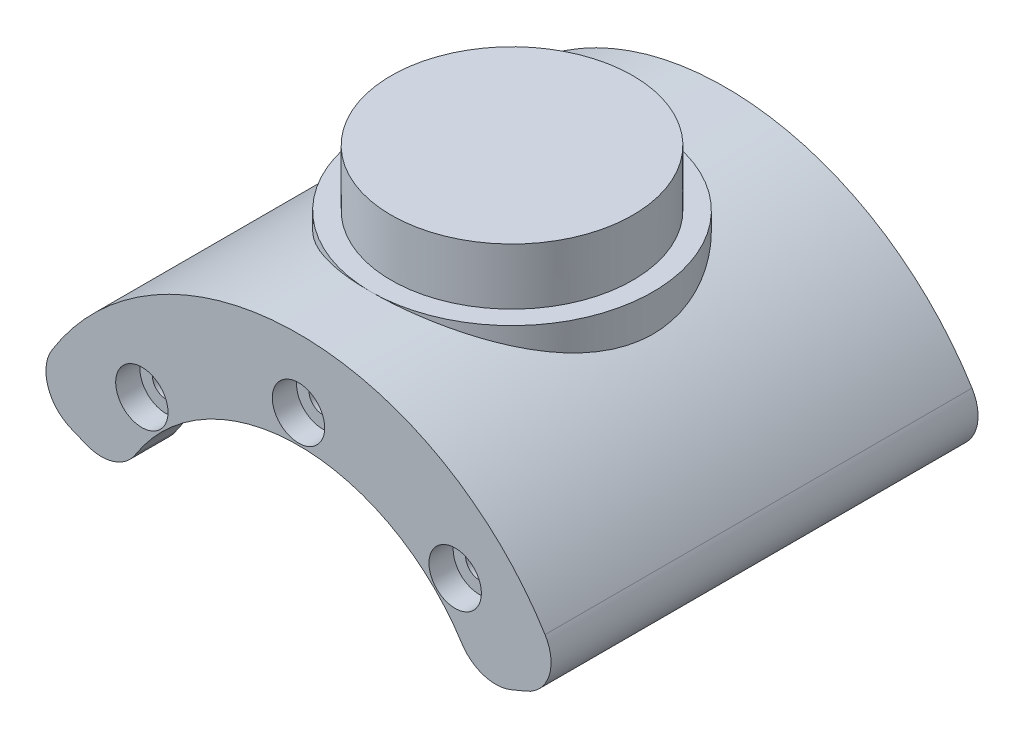
SolidWorks part; units mm, degrees
material "ABS"
ref_plane "Front" through (0, 0, 0) normal (0, 0, 1) x (1, 0, 0)
ref_plane "Top" through (0, 0, 0) normal (0, 1, 0) x (1, 0, 0)
ref_plane "Right" through (0, 0, 0) normal (1, 0, 0) x (0, 0, -1)
sketch "ｽｹｯﾁ1" plane through (0, 0, 0) normal (0, 0, 1) x (1, 0, 0)
  circle A0 centre (0, 0) radius 36
  dimension "D1" = 72
extrude "ﾎﾞｽ - 押し出し1" add sketch "ｽｹｯﾁ1" along normal mid plane 53
sketch "ｽｹｯﾁ5" plane through (0, 0, 0) normal (0, 0, 1) x (1, 0, 0)
  circle A0 centre (0, 0) radius 24
  dimension "D1" = 48
extrude "ｶｯﾄ - 押し出し3" cut sketch "ｽｹｯﾁ5" against normal through all both and the other way through all
sketch "ｽｹｯﾁ6" plane through (0, 0, 26.5) normal (0, 0, 1) x (1, 0, 0)
  line L0 (-33.2597, 13.7766) -> (0, 0)
  line L1 (0, 0) -> (33.2597, 13.7766)
  circle A0 centre (0, 0) radius 36 construction
  arc A1 (-33.2597, 13.7766) -> (33.2597, 13.7766) centre (0, 0) ccw
  dimension "D1" = 135
extrude "ｶｯﾄ - 押し出し4" cut sketch "ｽｹｯﾁ6" against normal through all both and the other way through all
sketch "ｽｹｯﾁ3" plane through (0, 0, 0) normal (0, 0, 1) x (1, 0, 0)
  line L0 (0, 0) -> (-33.2597, 13.7766) construction
  line L1 (0, 0) -> (33.2597, 13.7766) construction
  line L2 (-36, 0) -> (36, 0) construction
  line L3 (-33.2597, 13.7766) -> (-28.6403, 11.8632)
  line L4 (33.2597, 13.7766) -> (28.6403, 11.8632)
  line L6 (-22.1731, 9.1844) -> (-33.2597, 13.7766) construction
  circle A0 centre (0, 0) radius 31 construction
  circle A1 centre (0, 0) radius 36 construction
  arc A2 (-28.6403, 11.8632) -> (28.6403, 11.8632) centre (0, 0) cw
  arc A3 (-33.2597, 13.7766) -> (33.2597, 13.7766) centre (0, 0) ccw
  dimension "D1" = 5
extrude "ｶｯﾄ - 押し出し2" cut sketch "ｽｹｯﾁ3" against normal mid plane 43
hole_wizard "M3 穴付きねじ用座ぐり穴1" positions "ｽｹｯﾁ7" profile "ｽｹｯﾁ8" counterbore size "M3" standard "JIS"
sketch "ｽｹｯﾁ7" plane through (0, 0, 26.5) normal (0, 0, 1) x (1, 0, 0)
  point P0 (0, 27.5)
  dimension "D1" = 27.5
sketch "ｽｹｯﾁ8" plane through (0, 27.5, 26.5) normal (1, 0, 0) x (0, -1, 0)
  line L0 (0, 0) -> (0, 5)
  line L1 (0, 5) -> (1.7, 5)
  line L3 (1.7, 5) -> (1.7, 3)
  line L4 (1.7, 3) -> (3.25, 3)
  line L5 (3.25, 3) -> (3.25, 0)
  line L7 (3.25, 0) -> (0, 0)
  line L11 (0, -6.35) -> (0, 107.95) construction
  dimension "通し穴の直径" = 3.4
  dimension "通し穴の深さ" = 5
  dimension "座ぐり穴の直径" = 6.5
  dimension "座ぐり穴の深さ" = 3
pattern_circular "円形ﾊﾟﾀｰﾝ1" count 2 every 45 about axis through (0, 0, 26.5) along (0, 0, -1) of "M3 穴付きねじ用座ぐり穴1"
mirror "ﾐﾗｰ1" about plane through (0, 0, 0) normal (0, 0, 1) of "円形ﾊﾟﾀｰﾝ1", "M3 穴付きねじ用座ぐり穴1"
fillet "ﾌｨﾚｯﾄ1" radius 5 6 edges at (22.1731, 9.1844, -24) (22.1731, 9.1844, 24) (-22.1731, 9.1844, -24) (-22.1731, 9.1844, 24)
ref_plane "平面1" through (0, 31, 0) normal (0, -1, 0) x (-1, 0, 0)
ref_plane "平面2" through (0, 36, 0) normal (0, 1, 0) x (1, 0, 0)
sketch "ｽｹｯﾁ10" plane through (0, 31, 0) normal (0, -1, 0) x (-1, 0, 0)
  circle A0 centre (0, 0) radius 17.5
  dimension "D1" = 35
extrude "ﾎﾞｽ - 押し出し2" add sketch "ｽｹｯﾁ10" against normal through all
fillet "ﾌｨﾚｯﾄ2" [suppressed] radius 3
ref_plane "平面3" through (0, 21, 0) normal (0, -1, 0) x (-1, 0, 0)
sketch "ｽｹｯﾁ17" plane through (0, 36, 0) normal (0, 1, 0) x (1, 0, 0)
  circle A0 centre (0, 0) radius 15
  dimension "D1" = 30
extrude "ﾎﾞｽ - 押し出し3" add sketch "ｽｹｯﾁ17" along normal blind 7
